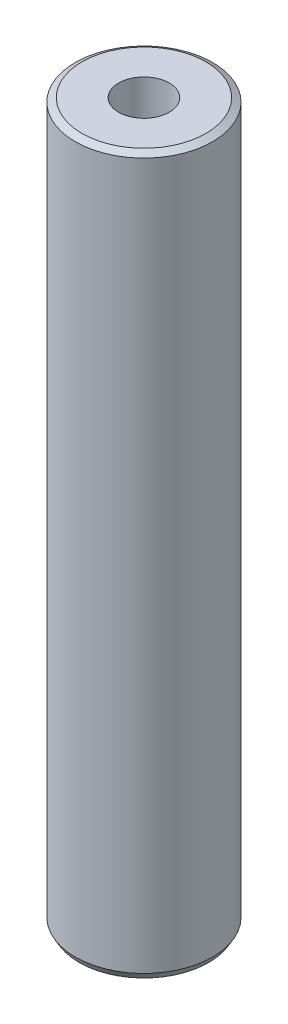
SolidWorks part; units mm, degrees
ref_plane "Front Plane" through (0, 0, 0) normal (0, 0, 1) x (1, 0, 0)
ref_plane "Top Plane" through (0, 0, 0) normal (0, 1, 0) x (1, 0, 0)
ref_plane "Right Plane" through (0, 0, 0) normal (1, 0, 0) x (0, 0, -1)
sketch "Sketch1" plane through (0, 0, 0) normal (0, 1, 0) x (1, 0, 0)
  circle A0 centre (0, 0) radius 57.5
  dimension "SHAFT_OD" = 115
extrude "Boss-Extrude1" add sketch "Sketch1" along normal blind 600
sketch "Sketch2" plane through (0, 0, 0) normal (0, 1, 0) x (1, 0, 0)
  circle A0 centre (0, 0) radius 21.2208
  dimension "BORE_D" = 42.4416
extrude "Cut-Extrude1" cut sketch "Sketch2" along normal through all
chamfer "Chamfer1" distance 3.2202 angle 60 2 edges at (0, 600, 57.5) (0, 0, 57.5) first distance on face at (0, 600, 57.5) first distance on face at (0, 0, 21.2208)
